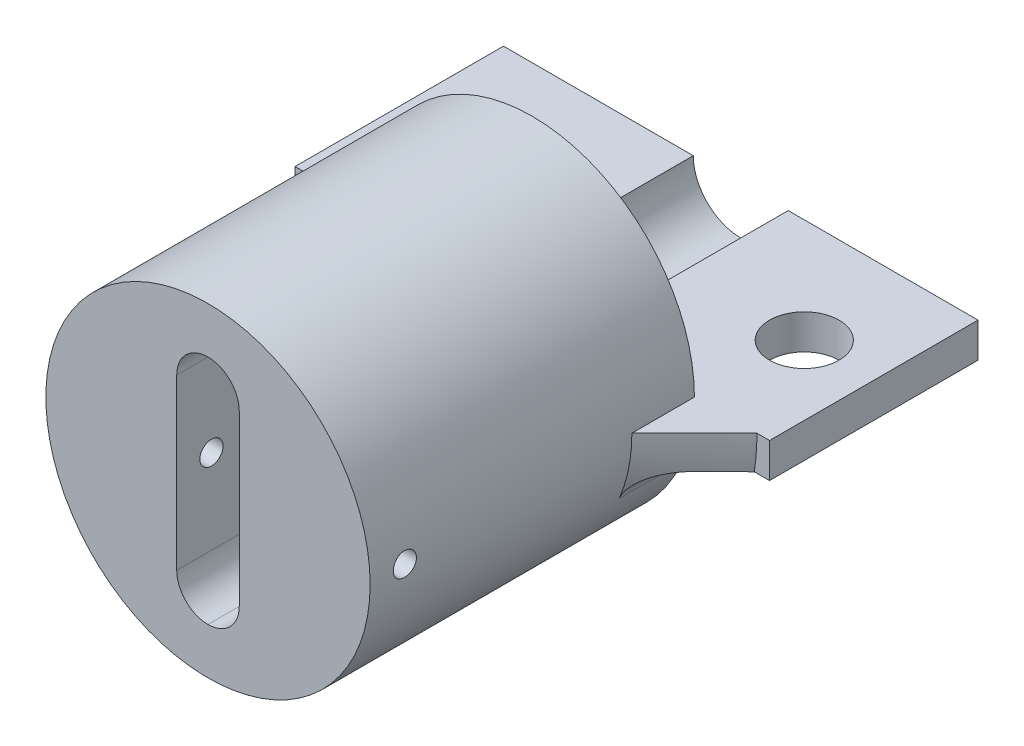
SolidWorks part; units mm, degrees
ref_plane "Front Plane" through (0, 0, 0) normal (0, 0, 1) x (1, 0, 0)
ref_plane "Top Plane" through (0, 0, 0) normal (0, 1, 0) x (1, 0, 0)
ref_plane "Right Plane" through (0, 0, 0) normal (1, 0, 0) x (0, 0, -1)
sketch "Sketch1" plane through (0, 0, 0) normal (0, 0, 1) x (1, 0, 0)
  line L0 (0, 0) -> (5, 0) construction
  line L1 (5, 0) -> (-5, 0) construction
  circle A0 centre (0, 0) radius 7
  dimension "D1" = 14
extrude "Boss-Extrude1" add sketch "Sketch1" along normal blind 4
sketch "Sketch2" plane through (0, 0, 4) normal (0, 0, 1) x (1, 0, 0)
  circle A0 centre (0, 0) radius 5
  circle A1 centre (0, 0) radius 7
  circle A2 centre (0, 0) radius 7
  dimension "D2" = 10
  dimension "D1" = 0
extrude "Boss-Extrude2" add sketch "Sketch2" along normal blind 10
sketch "Sketch3" plane through (0, 0, 4) normal (0, 0, 1) x (1, 0, 0)
  line L0 (-1.35, 4.8143) -> (-1.35, -4.8143)
  line L1 (1.35, 4.8143) -> (1.35, -4.8143)
  circle A1 centre (0, 0) radius 5
  arc A2 (1.35, -4.8143) -> (1.35, 4.8143) centre (0, 0) ccw
  arc A3 (-1.35, 4.8143) -> (-1.35, -4.8143) centre (0, 0) ccw
  dimension "D2" = 1.35
  dimension "D3" = 1.35
  dimension "D1" = 0
extrude "Boss-Extrude3" add sketch "Sketch3" along normal blind 10
sketch "Sketch4" plane through (0, 0, 0) normal (0, 0, -1) x (-1, 0, 0)
  line L2 (2.05, 0) -> (4.2426, 0)
  line L3 (-2.05, 0) -> (-4.2426, 0)
  line L7 (-4.2426, -1.5) -> (-10.2426, -1.5)
  line L9 (-4.2426, 0) -> (-10.2426, 0)
  line L10 (-10.2426, -1.5) -> (-10.2426, 0)
  line L11 (4.2426, -1.5) -> (10.2426, -1.5)
  line L13 (4.2426, 0) -> (10.2426, 0)
  line L14 (10.2426, -1.5) -> (10.2426, 0)
  arc A3 (-2.05, 0) -> (2.05, 0) centre (0, 0) ccw
  arc A7 (-4.2426, -1.5) -> (4.2426, -1.5) centre (0, 0) ccw
  circle A8 centre (0, 0) radius 7 construction
  dimension "D1" = 4.1
  dimension "D2" = 4.5
  dimension "D3" = 1.5
  dimension "D5" = 6
  dimension "D6" = 6
extrude "Boss-Extrude4" add sketch "Sketch4" along normal blind 9
fillet "Fillet3" radius 1.35 6 edges at (1.35, -4.8143, 9) (-1.35, -4.8143, 9) (1.35, 4.8143, 9) (-1.35, 4.8143, 9) (1.35, 0, 4) (-1.35, 0, 4)
sketch "Sketch7" plane through (0, 0, 0) normal (0, 1, 0) x (1, 0, 0)
  line L0 (10.2426, 9) -> (10.2426, 0) construction
  line L3 (7, 0) -> (-7, 0) construction
  line L4 (-10.2426, 9) -> (-10.2426, 0) construction
  line L7 (-10.2426, 0) -> (-7, 0) construction
  circle A0 centre (7.2426, 4.5) radius 1.5
  circle A1 centre (-7.2426, 4.5) radius 1.5
  point P18 (0, 0)
  dimension "D1" = 3
  dimension "D3" = 3
  dimension "D2" = 4.5
  dimension "D4" = 3
  dimension "D5" = 3
  dimension "D6" = 4.5
chamfer "Chamfer1" distance 2.7 angle 45 2 edges at (-6.9592, -0.7544, 0) (6.9592, -0.7544, 0)
extrude "Cut-Extrude1" cut sketch "Sketch7" against normal blind 10
fillet "Fillet4" radius 2 5 edges at (-6.8374, -1.5, 1.35) (6.8374, -1.5, 1.35) (-5.54, -1.5, 0) (5.54, -1.5, 0) (0, -4.5, 0)
ref_plane "Plane1" through (8.65, 0, 0) normal (1, 0, 0) x (0, 0, -1)
sketch "Sketch8" plane through (8.65, 0, 0) normal (1, 0, 0) x (0, 0, -1)
  circle A0 centre (-12.5, 0) radius 0.5
  dimension "D2" = 1
extrude "Cut-Extrude2" cut sketch "Sketch8" against normal through all contours A0
